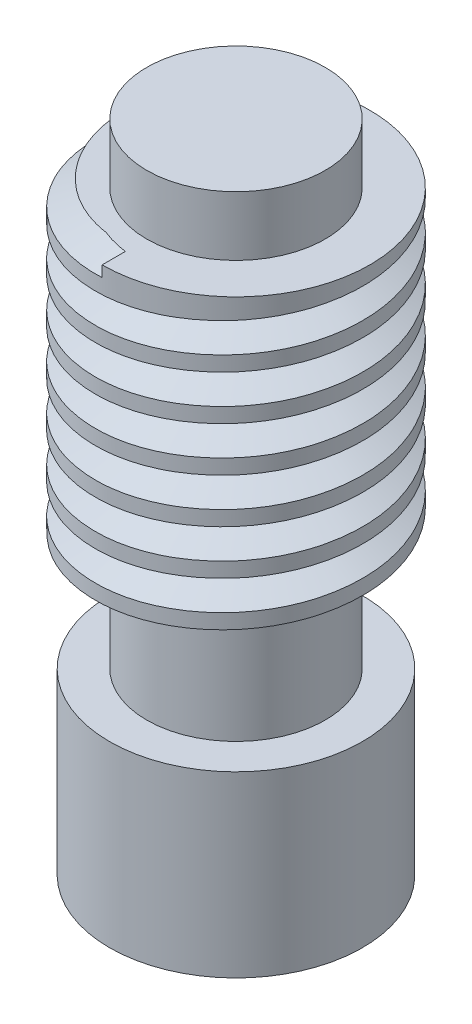
SolidWorks part; units mm, degrees
ref_plane "Спереди" through (0, 0, 0) normal (0, 0, 1) x (1, 0, 0)
ref_plane "Сверху" through (0, 0, 0) normal (0, 1, 0) x (1, 0, 0)
ref_plane "Справа" through (0, 0, 0) normal (1, 0, 0) x (0, 0, -1)
sketch "Эскиз1" plane through (0, 0, 0) normal (0, 1, 0) x (1, 0, 0)
  circle A0 centre (0, 0) radius 2
  circle A1 centre (0, 0) radius 4.25
extrude "Вытянуть1" add sketch "Эскиз1" along normal blind 6
sketch "Эскиз2" plane through (0, 6, 0) normal (0, 1, 0) x (-1, 0, 0)
  circle A0 centre (0, 0) radius 2
  circle A1 centre (0, 0) radius 3
extrude "Вытянуть2" add sketch "Эскиз2" along normal blind 4
sketch "Эскиз3" plane through (0, 10, 0) normal (0, 1, 0) x (1, 0, 0)
  circle A0 centre (0, 0) radius 4.5
extrude "Вытянуть3" add sketch "Эскиз3" along normal blind 10
sketch "Эскиз4" plane through (0, 20, 0) normal (0, 1, 0) x (1, 0, 0)
  circle A0 centre (0, 0) radius 3
extrude "Вытянуть4" add sketch "Эскиз4" along normal blind 2
sketch "Эскиз5" plane through (0, 10, 0) normal (0, -1, 0) x (1, 0, 0)
  circle A0 centre (0, 0) radius 4
curve "Спираль1" pitch 1.5 height 10.5 turns 7
sketch "Эскиз6" plane through (0, 0, 0) normal (0, 0, 1) x (1, 0, 0)
  line L0 (4.5, 12.0052) -> (4.5, 11.0052)
  line L1 (4.5, 10) -> (4.5, 20) construction
  line L2 (4.5, 11.0052) -> (3.5962, 11.4331)
  line L3 (3.5962, 11.4331) -> (4.5, 12.0052)
sweep "Вырез-По траектории1" cut profiles "Эскиз6" path "Спираль1"
